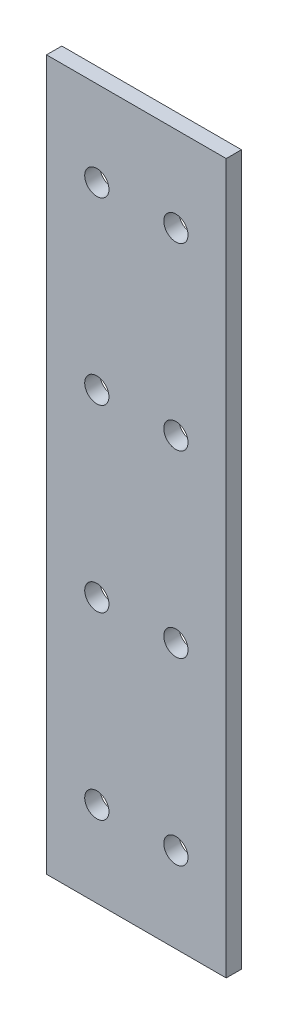
SolidWorks part; units mm, degrees
material "ABS"
ref_plane "Front Plane" through (0, 0, 0) normal (0, 0, 1) x (1, 0, 0)
ref_plane "Top Plane" through (0, 0, 0) normal (0, 1, 0) x (1, 0, 0)
ref_plane "Right Plane" through (0, 0, 0) normal (1, 0, 0) x (0, 0, -1)
sketch "Sketch1" plane through (0, 0, 0) normal (0, 0, 1) x (1, 0, 0)
  line L1 (-10, -39.5) -> (10, -39.5)
  line L2 (-10, -39.5) -> (-10, 39.5)
  line L3 (-10, 39.5) -> (10, 39.5)
  line L4 (10, -39.5) -> (10, 39.5)
  line L5 (-10, -39.5) -> (10, 39.5) construction
  line L6 (-10, 39.5) -> (10, -39.5) construction
  point P0 (0, 0)
  dimension "D1" = 20
  dimension "D2" = 79
extrude "Boss-Extrude1" add sketch "Sketch1" along normal blind 1.7
sketch "Sketch3" plane through (0, 0, 1.7) normal (0, 0, 1) x (1, 0, 0)
  line L0 (0, 0) -> (0, 39.5) construction
  line L1 (10, 39.5) -> (-10, 39.5) construction
  line L2 (0, 0) -> (-4.4, -10) construction
  line L3 (-4.4, 10) -> (0, 0) construction
  circle A0 centre (-4.4, 30) radius 1.35
  circle A1 centre (-4.4, 10) radius 1.35
  circle A2 centre (-4.4, -10) radius 1.35
  circle A3 centre (-4.4, -30) radius 1.35
  circle A4 centre (4.4, -30) radius 1.35
  circle A5 centre (4.4, -10) radius 1.35
  circle A6 centre (4.4, 10) radius 1.35
  circle A7 centre (4.4, 30) radius 1.35
  dimension "D1" = 2.7
  dimension "D2" = 4.4
  dimension "D4" = 20
  dimension "D3" = 4
extrude "Cut-Extrude1" cut sketch "Sketch3" against normal through all
equation "\"smallPulleyTeeth\"= 30"
equation "\"largePulleyTeeth\"= 30"
equation "\"eighthThick\"= 3.0mm"
equation "\"sixteenthThick\"= 1.7mm"
equation "\"quarterThick\"=6.0mm"
equation "\"OD\"= 145mm"
equation "\"puckAngle\"= 60.5deg"
equation "\"puckDiam\"= 76.5mm"
equation "\"puckDist\"= 85mm"
equation "\"scoopFillet\"= 5mm"
equation "\"axlePress\"= 5.9mm"
equation "\"press\"= 0.2mm"
equation "\"wheelClear\"= 0.3mm"
equation "\"10-32clear\"= 4.8mm"
equation "\"10-32tap\"= 4.45mm"
equation "\"6-32clear\"= 3.3mm"
equation "\"8-32clear\"= 4.0mm"
equation "\"4-40clear\"= 3.0mm"
equation "\"wheelHeight\"= 22mm"
equation "\"wheelWell\"= 65mm"
equation "\"ledSmall\"= 3.1mm"
equation "\"ledLarge\"= 4.2mm"
equation "\"ledLength\"= 4.2mm"
equation "\"4-40close\"= 2.7mm"
equation "\"4-40nutThick\"= 2.2mm"
equation "\"4-40nutWidth\"= 6.2mm"
equation "\"4-40insertHeight\"= 3.5mm"
equation "\"4-40insert\"= 4.25mm"
equation "\"D1@Boss-Extrude1\"=\"sixteenthThick\""
equation "\"D1@Sketch3\"=\"4-40close\""
